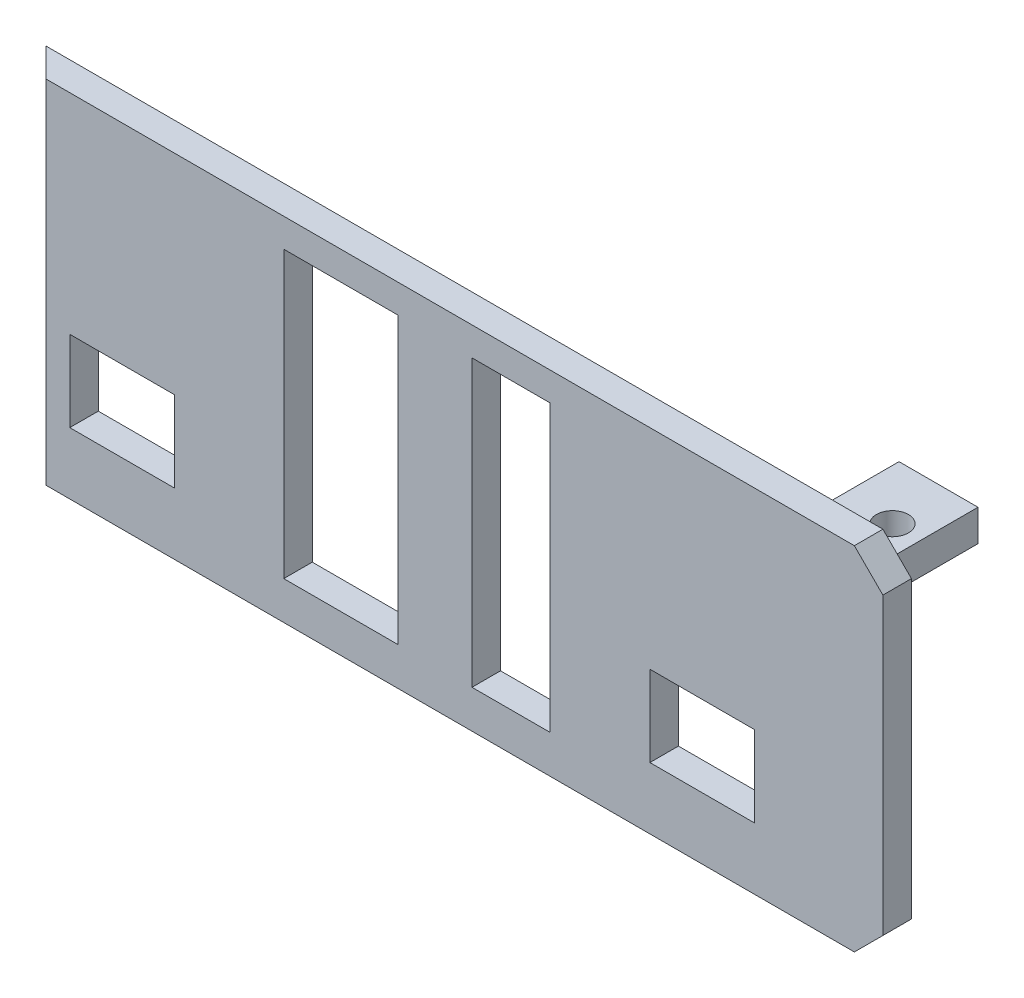
SolidWorks part; units mm, degrees
ref_plane "前视基准面" through (0, 0, 0) normal (0, 0, 1) x (1, 0, 0)
ref_plane "上视基准面" through (0, 0, 0) normal (0, 1, 0) x (1, 0, 0)
ref_plane "右视基准面" through (0, 0, 0) normal (1, 0, 0) x (0, 0, -1)
other "Configuration Table"
sketch "草图1" plane through (0, 0, 0) normal (0, 0, 1) x (1, 0, 0)
  line L1 (-45.5, -18.5) -> (45.5, -18.5)
  line L2 (-45.5, -18.5) -> (-45.5, 18.5)
  line L3 (-45.5, 18.5) -> (45.5, 18.5)
  line L4 (45.5, -18.5) -> (45.5, 18.5)
  line L5 (-45.5, -18.5) -> (45.5, 18.5) construction
  line L6 (-45.5, 18.5) -> (45.5, -18.5) construction
  point P0 (0, 0)
  dimension "D1" = 91
  dimension "D2" = 37
extrude "凸台-拉伸1" add sketch "草图1" along normal blind 3
chamfer "倒角1" distance 3 angle 45 1 edges at (-45.5, 0, 3)
sketch "草图2" plane through (0, 0, 3) normal (0, 0, 1) x (1, 0, 0)
  line L0 (-39, -4.5) -> (-39, -11) construction
  line L1 (-40, -12) -> (-29, -12)
  line L2 (-40, -12) -> (-40, -3.5)
  line L3 (-40, -3.5) -> (-29, -3.5)
  line L4 (-29, -12) -> (-29, -3.5)
  line L5 (21, -12) -> (32, -12)
  line L6 (21, -12) -> (21, -3.5)
  line L7 (21, -3.5) -> (32, -3.5)
  line L8 (32, -12) -> (32, -3.5)
  line L9 (-39, -11) -> (-30, -11) construction
  line L10 (-39, -4.5) -> (-30, -4.5) construction
  line L11 (-30, -4.5) -> (-30, -11) construction
  line L12 (22, -4.5) -> (22, -11) construction
  line L13 (22, -11) -> (31, -11) construction
  line L14 (22, -4.5) -> (31, -4.5) construction
  line L15 (31, -4.5) -> (31, -11) construction
  point P18 (21, -7.75)
  dimension "D1" = 1
  dimension "D2" = 1
  dimension "D3" = 1
  dimension "D4" = 1
  dimension "D5" = 1
  dimension "D6" = 1
  dimension "D7" = 1
  dimension "D8" = 1
extrude "切除-拉伸1" cut sketch "草图2" against normal blind 10
sketch "草图3" plane through (0, 0, 0) normal (0, 0, -1) x (-1, 0, 0)
  line L0 (71.6716, 15.5) -> (47.5, 15.5) construction
  line L1 (17.5, 15.5) -> (5.5, 15.5)
  line L2 (17.5, 15.5) -> (17.5, -14.5)
  line L3 (17.5, -14.5) -> (5.5, -14.5)
  line L4 (5.5, 15.5) -> (5.5, -14.5)
  line L5 (-42.5, -14.5) -> (33.5, -14.5) construction
  line L6 (12.5, 14) -> (12.5, -11) construction
  line L7 (5.5, 14) -> (5.5, -10.5) construction
  line L8 (-10.5, -10) -> (-10.5, -49) construction
  line L9 (-2.2925, 15.5) -> (-10.5, 15.5)
  line L10 (-2.2925, 15.5) -> (-2.2925, -14.5)
  line L11 (-2.2925, -14.5) -> (-10.5, -14.5)
  line L12 (-10.5, 15.5) -> (-10.5, -14.5)
  dimension "D1" = 5
  dimension "D2" = 0
extrude "切除-拉伸2" cut sketch "草图3" against normal blind 10
sketch "草图4" plane through (0, 0, 0) normal (0, 0, -1) x (-1, 0, 0)
  line L1 (-42.5, 15.5) -> (-34.1947, 15.5)
  line L2 (-42.5, 15.5) -> (-42.5, 12.1807)
  line L3 (-42.5, 12.1807) -> (-34.1947, 12.1807)
  line L4 (-34.1947, 15.5) -> (-34.1947, 12.1807)
extrude "凸台-拉伸2" add sketch "草图4" along normal blind 10
sketch "草图5" plane through (0, 15.5, 0) normal (0, 1, 0) x (1, 0, 0)
  circle A0 centre (39.5, 4) radius 1.6838
extrude "切除-拉伸3" cut sketch "草图5" against normal blind 10
chamfer "倒角2" distance 3 angle 45 1 edges at (45.5, 18.5, 1.5)
chamfer "倒角3" distance 3 angle 45 1 edges at (45.5, -18.5, 1.5)
